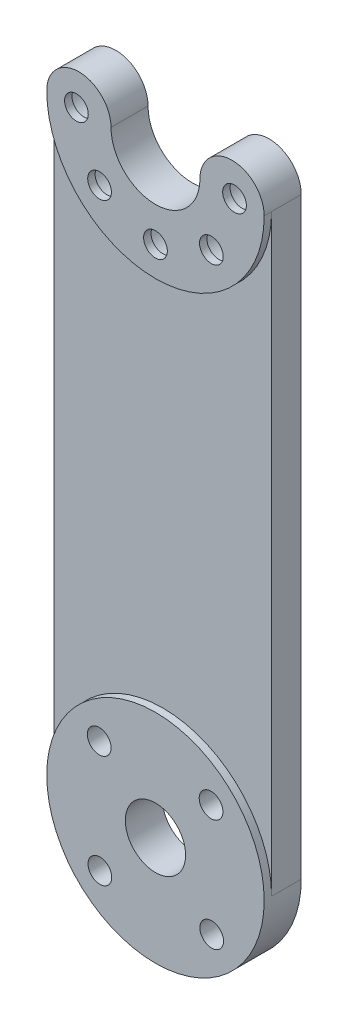
SolidWorks part; units mm, degrees
ref_plane "Plano frontal" through (0, 0, 0) normal (0, 0, 1) x (1, 0, 0)
ref_plane "Plano superior" through (0, 0, 0) normal (0, 1, 0) x (1, 0, 0)
ref_plane "Plano direito" through (0, 0, 0) normal (1, 0, 0) x (0, 0, -1)
sketch "Esboço1" plane through (0, 0, 0) normal (0, 0, 1) x (1, 0, 0)
  arc A2 (-4.5, 0) -> (4.5, 0) centre (0, 0) ccw
  arc A3 (11, 0) -> (-11, 0) centre (0, 0) cw
  arc A4 (-4, 0) -> (4, 0) centre (0, 0) ccw construction
  arc A5 (11, 0) -> (4.5, 0) centre (7.75, 0) ccw
  arc A6 (-4.5, 0) -> (-11, 0) centre (-7.75, 0) ccw
  arc A9 (-11, 0) -> (11, 0) centre (0, 0) ccw construction
  dimension "D1" = 0.5
extrude "Ressalto-extrusão1" add sketch "Esboço1" against normal offset from surface (0.75 mm away) 2 offset beyond the face yes
sketch "Esboço3" plane through (0, 0, -0.75) normal (0, 0, -1) x (-1, 0, 0)
  line L0 (-11, 0) -> (-11, -60)
  line L2 (11, -60) -> (11, 0)
  arc A0 (11, 0) -> (4.5, 0) centre (7.75, 0) ccw construction
  arc A1 (-4.5, 0) -> (4.5, 0) centre (0, 0) ccw construction
  arc A2 (-4.5, 0) -> (-11, 0) centre (-7.75, 0) ccw construction
  arc A3 (11, 0) -> (4.5, 0) centre (7.75, 0) ccw
  arc A4 (-4.5, 0) -> (4.5, 0) centre (0, 0) ccw
  arc A5 (-4.5, 0) -> (-11, 0) centre (-7.75, 0) ccw
  arc A9 (-11, -60) -> (11, -60) centre (0, -60) ccw
extrude "Ressalto-extrusão2" add sketch "Esboço3" along normal blind 3
hole_wizard "Rebaixo para SHCS M21" positions "Sketch1" profile "Sketch2" counterbore size "M2" standard "Ansi Metric" end condition up to next
sketch "Sketch1" plane through (0, 0, -3.75) normal (0, 0, -1) x (-1, 0, 0)
  line L0 (0, 0) -> (-8, 0) construction
  line L1 (0, 0) -> (-5.6569, -5.6569) construction
  line L2 (0, 0) -> (0, -8) construction
  line L3 (0, 0) -> (5.6569, -5.6569) construction
  line L4 (0, 0) -> (8, 0) construction
  arc A0 (-9, 0) -> (-7, 0) centre (-8, 0) ccw construction
  point P0 (-8, 0)
  point P16 (-5.6569, -5.6569)
  point P18 (0, -8)
  point P20 (5.6569, -5.6569)
  point P22 (8, 0)
  dimension "D1" = 5
sketch "Sketch2" plane through (8, 0, -3.75) normal (1, 0, 0) x (0, 1, 0)
  line L0 (0, 0) -> (0, 3.75)
  line L1 (0, 3.75) -> (1.2, 3.75)
  line L3 (1.2, 3.75) -> (1.2, 3)
  line L4 (1.2, 3) -> (2.2, 3)
  line L5 (2.2, 3) -> (2.2, 0)
  line L7 (2.2, 0) -> (0, 0)
  line L11 (0, -6.35) -> (0, 107.95) construction
  dimension "Thru Hole Dia." = 2.4
  dimension "Thru Hole Depth" = 3.75
  dimension "C'Bore Dia." = 4.4
  dimension "C'Bore Depth" = 3
sketch "Esboço4" plane through (0, 0, -0.75) normal (0, 0, 1) x (1, 0, 0)
  circle A0 centre (0, -60) radius 11
  arc A1 (-11, -60) -> (11, -60) centre (0, -60) ccw construction
extrude "Ressalto-extrusão3" add sketch "Esboço4" along normal up to surface (0.75 mm away)
sketch "Esboço5" plane through (0, 0, -3.75) normal (0, 0, -1) x (-1, 0, 0)
  circle A0 centre (0, -60) radius 3.05 construction
  circle A1 centre (0, -60) radius 3.05
extrude "Corte-extrusão1" cut sketch "Esboço5" against normal through all
hole_wizard "Rebaixo para parafuso com cabeça redonda de M21" positions "Esboço6" profile "Esboço7" counterbore size "M2" standard "DIN" end condition up to next
sketch "Esboço6" plane through (0, 0, -3.75) normal (0, 0, -1) x (-1, 0, 0)
  circle A0 centre (5.6247, -65.6888) radius 0.8 construction
  point P0 (5.6247, -65.6888)
sketch "Esboço7" plane through (-5.6247, -65.6888, -3.75) normal (1, 0, 0) x (0, 1, 0)
  line L0 (0, 0) -> (0, 3.75)
  line L1 (0, 3.75) -> (1.2, 3.75)
  line L3 (1.2, 3.75) -> (1.2, 1.4)
  line L4 (1.2, 1.4) -> (2.2, 1.4)
  line L5 (2.2, 1.4) -> (2.2, 0)
  line L7 (2.2, 0) -> (0, 0)
  line L11 (0, -6.35) -> (0, 107.95) construction
  dimension "Thru Hole Dia." = 2.4
  dimension "Thru Hole Depth" = 3.75
  dimension "C'Bore Dia." = 4.4
  dimension "C'Bore Depth" = 1.4
pattern_circular "PadrãoCircular1" count 4 over 360 about axis through (0, -60, -3.75) along (0, 0, -1) of "Rebaixo para parafuso com cabeça redonda de M21"
